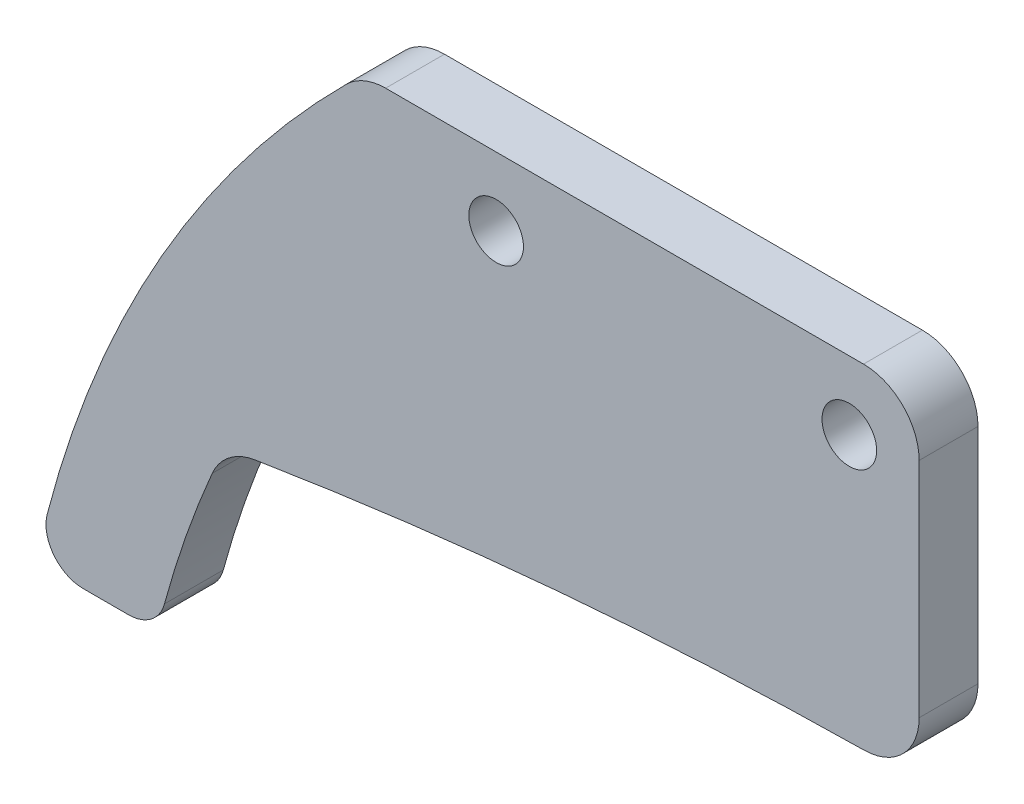
SolidWorks part; units mm, degrees
material "Delrin 2700 NC010, Low Viscosity Acetal Copolymer (SS)"
ref_plane "Front Plane" through (0, 0, 0) normal (0, 0, 1) x (1, 0, 0)
ref_plane "Top Plane" through (0, 0, 0) normal (0, 1, 0) x (1, 0, 0)
ref_plane "Right Plane" through (0, 0, 0) normal (1, 0, 0) x (0, 0, -1)
sketch "Sketch1" plane through (0, 0, 0) normal (0, 0, 1) x (1, 0, 0)
  line L1 (-17.1227, 44.5) -> (-47.1227, 44.5)
  line L3 (-17.1227, 26.5) -> (-17.1227, 44.5)
  line L4 (-17.1227, 26.5) -> (-9.8773, 26.5) construction
  line L7 (-17.1227, 44.5) -> (-47.1227, 44.5)
  line L12 (-58.2093, 12.9656) -> (-64.7502, 12.9656)
  arc A0 (-17.1227, 26.5) -> (-54.5777, 23.3401) centre (-17.1227, -197.0625) ccw
  arc A2 (-47.1227, 44.5) -> (-60.1383, 26.5) centre (-4.5353, 0) ccw
  arc A3 (-47.1227, 44.5) -> (-64.7502, 12.9656) centre (-4.5353, 0) ccw
  arc A4 (-54.5777, 23.3401) -> (-58.2093, 12.9656) centre (-4.5353, 0) ccw
  dimension "D3" = 61.595
  dimension "D2" = 18
  dimension "D1" = 18
  dimension "D4" = 30
extrude "Boss-Extrude1" add sketch "Sketch1" along normal blind 3.175 contours L1 A2 region at (-39.0581, 32.8079, 0)
sketch "Sketch2" plane through (0, 0, 3.175) normal (0, 0, 1) x (1, 0, 0)
  circle A10 centre (-20.8896, 40.8119) radius 1.4732
  circle A11 centre (-39.9396, 40.8119) radius 1.4732
extrude "Cut-Extrude1" cut sketch "Sketch2" against normal through all
fillet "Fillet1" radius 3 4 edges at (-47.1227, 44.5, 1.5875) (-17.1227, 26.5, 1.5875) (-17.1227, 44.5, 1.5875) (-54.5777, 23.3401, 1.5875)
fillet "Fillet3" radius 2 2 edges at (-64.7502, 12.9656, 1.5875) (-58.2093, 12.9656, 1.5875)
